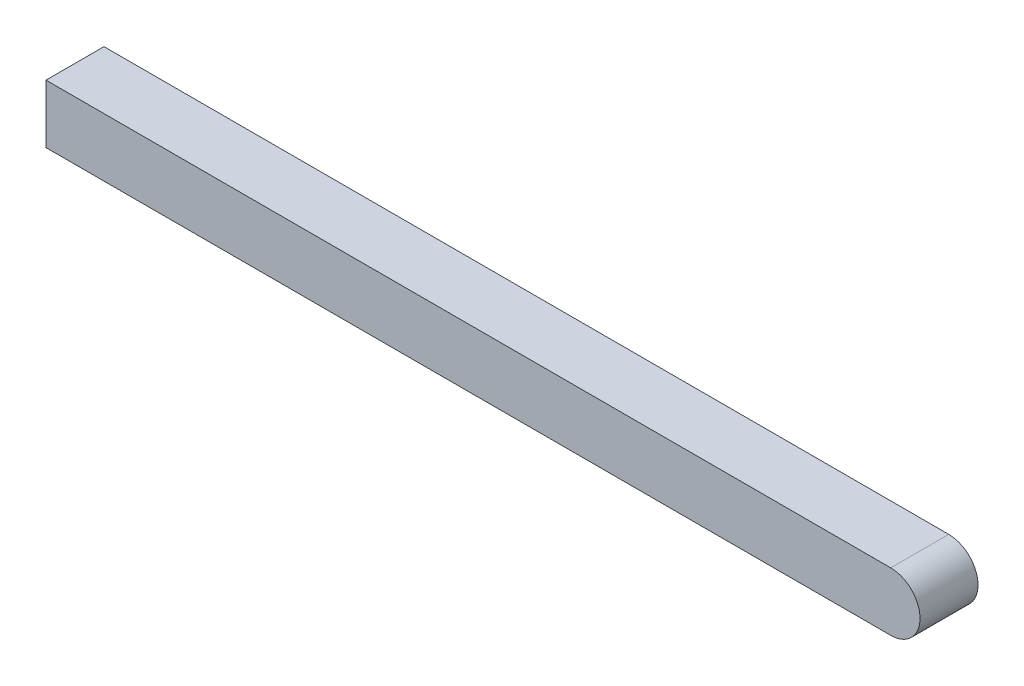
SolidWorks part; units mm, degrees
ref_plane "Спереди" through (0, 0, 0) normal (0, 0, 1) x (1, 0, 0)
ref_plane "Сверху" through (0, 0, 0) normal (0, 1, 0) x (1, 0, 0)
ref_plane "Справа" through (0, 0, 0) normal (1, 0, 0) x (0, 0, -1)
other "Configuration Table"
sketch "Ширина_фанера_плюс_зазор" plane through (0, 0, 0) normal (0, 0, 1) x (1, 0, 0)
  line L0 (-0.1, -9.075) -> (262.075, -9.075)
  line L1 (262.075, -9.075) -> (262.075, 9.075)
  line L2 (262.075, 9.075) -> (-0.1, 9.075)
  line L3 (-0.1, 9.075) -> (-0.1, -9.075)
  line L4 (-0.1, -9.075) -> (262.075, 9.075) construction
  point P4 (130.9875, 0)
  dimension "Ширина" = 262.175
  dimension "Глубина" = 18.15
  dimension "Положение_ПоОси" = 130.9875
extrude "Прямой_участок" add sketch "Ширина_фанера_плюс_зазор" along normal blind 18
sketch "Выход_фрезы6" plane through (0, 0, 0) normal (0, 0, 1) x (1, 0, 0)
  circle A0 centre (262.075, 0) radius 9.075
  dimension "Диаметр1" = 18.15
  dimension "Центр1_ПоОси" = 262.075
extrude "Круглый_конец" add sketch "Выход_фрезы6" along normal blind 18
equation "\"Диаметр1@Выход_фрезы6\"  = \"Толщина горизонтальных плит\"+\"Посадочный зазор\""
equation "\"Глубина@Ширина_фанера_плюс_зазор\"  = \"Толщина горизонтальных плит\"+\"Посадочный зазор\""
equation "\"Фанера\"= \"Толщина горизонтальных плит\""
equation "\"Ширина шипа\"=16"
equation "\"Межосевое шипов\"=40"
equation "\"Посадочный зазор\"=0.15"
equation "\"Основная фреза\"=6"
equation "\"Мелкая фреза\"=6"
equation "\"Запас разгрузки\"=0.05"
equation "\"Ширина образца\"=84"
equation "\"Высота образца\"=50"
equation "\"Канал М6\"=6"
equation "\"Гайка под ключ\"=10.3"
equation "\"Длина кармана гайки\"=6.2"
equation "\"Отступ гайки\"=12"
equation "\"Ширина@Ширина_фанера_плюс_зазор\" = 262.175"
equation "\"Положение_ПоОси@Ширина_фанера_плюс_зазор\" =  ( 130.9875 ) "
equation "\"Центр1_ПоОси@Выход_фрезы6\" =  ( 262.075 ) "
equation "\"Ширина груза\"= 420"
equation "\"Глубина груза\"= 490"
equation "\"Высота груза\"= 297"
equation "\"Ширина ячейки\"= \"Ширина груза\" + 10"
equation "\"Глубина ячейки\"= \"Глубина груза\" + 10"
equation "\"Высота ячейки\"= \"Высота груза\" + 10 + 13"
equation "\"Колво ячеек ширина\"= 2"
equation "\"Колво ячеек высота\"= 2"
equation "\"Толщина стенки\" = \"Толщина тонких панелей\""
equation "\"Крепление дверцы\"= 5 "
equation "\"Ширина рейки\"= \"Толщина шестерни\""
equation "\"Высота рейки\"= 20"
equation "\"Высота пола\" = 2*\"Толщина тонких панелей\""
equation "\"Колво полозьев\"= 5"
equation "\"Отступ рейки\"= 20"
equation "\"Глубина каретки\"= \"Глубина ячейки\" + 30 + \"Мотор Y высота корпуса\" + 20"
equation "\"Длинна рейки\" = (\"Ширина ячейки\"+\"Толщина вертикальных стенок\"+\"Крепление дверцы\")*\"Колво ячеек ширина\"+\"Ширина ячейки выгрузки\"*\"Колво выгрузки\"+\"Толщина вертикальных стенок\"+2*\"Отступ крепления мотора фиксации\"-\"Крепление дверцы\"*\"Колво ячеек ширина\""
equation "\"Отступ шпильки\"= 26"
equation "\"Диаметр шпильки\"= 5"
equation "\"Длинна шпильки\" = (\"Высота ячейки\"+\"Толщина горизонтальных плит\"+\"Высота пола\")*\"Колво ячеек высота\"+2*(\"Толщина горизонтальных плит\"+\"Отступ рейки\")"
equation "\"Ширина пластины\"= 50  "
equation "\"Высота зона выгрузки\"= \"Высота ячейки\" * 2 + \"Толщина стенки\" * 2"
equation "\"Колво выгрузки\"= 1"
equation "\"Ширина ячейки выгрузки\" = \"Ширина ячейки\"+\"Толщина вертикальных стенок\"+2*\"Отступ крепления мотора фиксации\""
equation "\"Отступ крепления мотора фиксации\" = (\"Ширина пластины\"+20-\"Толщина вертикальных стенок\")/2"
equation "\"Мотор X ширина корпуса\"= 42.3"
equation "\"Мотор X высота корпуса\"= 42.3"
equation "\"Мотор X длина корпуса\"= 40"
equation "\"Мотор X вылет вала\"= 19.8"
equation "\"Мотор Y ширина корпуса\"= 42.3"
equation "\"Мотор Y высота корпуса\"= 42.3"
equation "\"Мотор Y длина корпуса\"= 48"
equation "\"Мотор Y вылет вала\"= 30"
equation "\"Мотор Z ширина корпуса\"= 42"
equation "\"Мотор Z высота корпуса\"= 42"
equation "\"Мотор Z длина корпуса\"= 40"
equation "\"Мотор Z вылет вала\"= 23"
equation "\"Мотор диаметр вала ПРЕДВ\"= 5"
equation "\"Мотор шаг крепления ПРЕДВ\"= 31"
equation "\"Мотор диаметр отверстий ПРЕДВ\"= 3"
equation "\"Мотор глубина отверстий ПРЕДВ\"= 4.5"
equation "\"Мотор диаметр буртика ПРЕДВ\"= 22"
equation "\"Мотор высота буртика ПРЕДВ\"= 2"
equation "\"Мотор диаметр шкива ПРЕДВ\"= 16"
equation "\"Мотор длина шкива ПРЕДВ\"= 12"
equation "\"Мотор отступ шкива ПРЕДВ\"= 5"
equation "\"Мотор X шаг градусов\"= 1.8"
equation "\"Мотор Y шаг градусов\"= 1.8"
equation "\"Мотор Z шаг градусов\"= 1.8"
equation "\"Мотор Y диаметр ротора\"= 25.78"
equation "\"Толщина шестерни\"= 10"
equation "\"Толщина тонких панелей\" = 6"
equation "\"Толщина вертикальных стенок\" = 18"
equation "\"Толщина горизонтальных плит\" = 18"
equation "\"Базовая высота корпуса\" = (\"Высота ячейки\"+\"Толщина тонких панелей\"+\"Высота пола\")*\"Колво ячеек высота\"+6*\"Толщина тонких панелей\"+\"Мотор X ширина корпуса\"+\"Мотор Y ширина корпуса\"+75"
equation "\"Высота корпуса\" = (\"Высота ячейки\"+\"Толщина горизонтальных плит\"+\"Высота пола\")*\"Колво ячеек высота\"+2*\"Толщина горизонтальных плит\"+4*\"Толщина тонких панелей\"+\"Мотор X ширина корпуса\"+\"Мотор Y ширина корпуса\"+75"
equation "\"Смещение центра корпуса\" = (\"Высота корпуса\"-\"Базовая высота корпуса\")/2-(\"Толщина горизонтальных плит\"-\"Толщина тонких панелей\")"
equation "\"Отметка пола\" = -\"Базовая высота корпуса\"/2+\"Толщина тонких панелей\""
equation "\"Отметка потолка\" = \"Отметка пола\"+\"Высота корпуса\"-2*\"Толщина горизонтальных плит\""
equation "\"Отметка верхней полки\" = \"Отметка потолка\"-(28+\"Толщина тонких панелей\")-\"Высота ячейки\"-\"Высота пола\""
equation "\"Отметка нижней полки\" = \"Отметка верхней полки\"-\"Высота ячейки\"-\"Высота пола\"-\"Толщина горизонтальных плит\""
